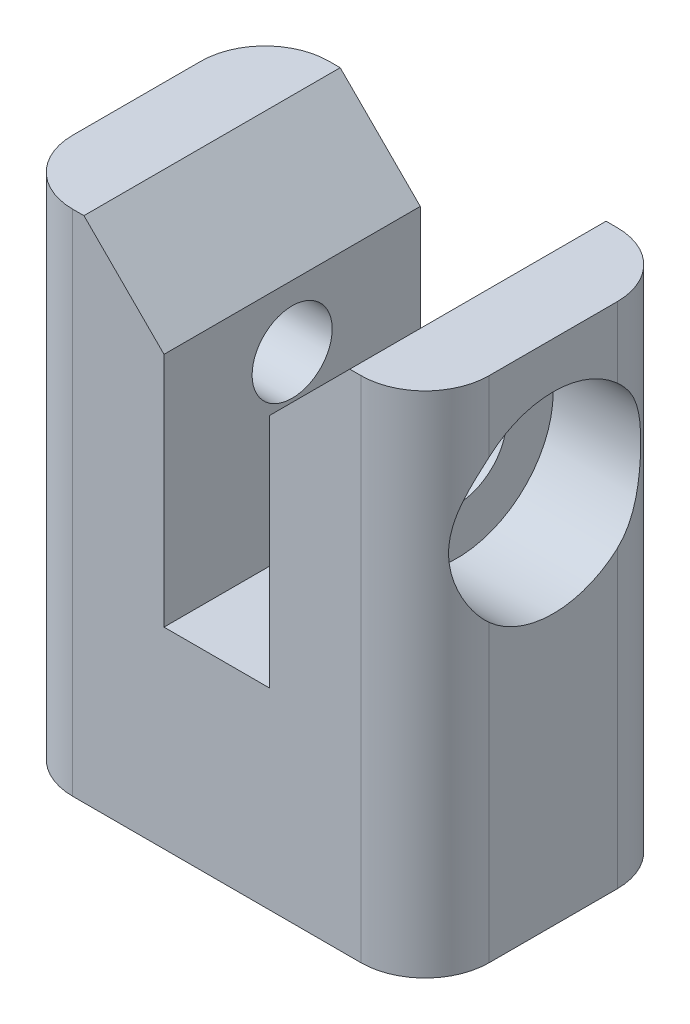
SolidWorks part; units mm, degrees
ref_plane "Front Plane" through (0, 0, 0) normal (0, 0, 1) x (1, 0, 0)
ref_plane "Top Plane" through (0, 0, 0) normal (0, 1, 0) x (1, 0, 0)
ref_plane "Right Plane" through (0, 0, 0) normal (1, 0, 0) x (0, 0, -1)
sketch "Sketch1" plane through (0, 0, 0) normal (0, 0, 1) x (1, 0, 0)
  line L0 (-6.5, 0) -> (6.5, 0)
  line L1 (6.5, 0) -> (6.5, 15.875)
  line L2 (6.5, 15.875) -> (1.65, 15.875)
  line L3 (1.65, 15.875) -> (1.65, 6)
  line L4 (1.65, 6) -> (-1.65, 6)
  line L5 (-1.65, 6) -> (-1.65, 15.875)
  line L6 (-1.65, 15.875) -> (-6.5, 15.875)
  line L7 (-6.5, 15.875) -> (-6.5, 0)
  point P0 (0, 6)
  point P4 (0, 0)
  dimension "D1" = 3.3
  dimension "D2" = 15.875
  dimension "D3" = 6
  dimension "D4" = 13
extrude "Boss-Extrude1" add sketch "Sketch1" along normal mid plane 8
sketch "Sketch2" plane through (6.5, 0, 0) normal (1, 0, 0) x (0, 0, -1)
  line L0 (-4, 6) -> (4, 6) construction
  point P0 (0, 11.4375)
  point P1 (0, 0)
  dimension "D1" = 5.4375
hole_wizard "M3x0.5 Tapped Hole1" positions "Sketch5" profile "Sketch6" tap size "M3x0.5" standard "ANSI Metric" end condition through all
sketch "Sketch5" plane through (6.5, 0, 0) normal (1, 0, 0) x (0, 0, -1)
  point P0 (0, 11.4375)
sketch "Sketch6" plane through (6.5, 11.4375, 0) normal (0, 1, 0) x (0, 0, -1)
  line L0 (0, 0) -> (0, 13)
  line L1 (0, 13) -> (1.25, 13)
  line L2 (1.25, 13) -> (1.25, 0)
  line L5 (1.25, 0) -> (0, 0)
  line L11 (0, -6.35) -> (0, 107.95) construction
  dimension "Thru Tap Drill Dia." = 2.5
  dimension "Thru Tap Drill Depth" = 13
cosmetic thread "Hole Thread1" parameters "D2"=3
hole_wizard "CBORE for M3 SHCS1" positions "Sketch3" profile "Sketch4" counterbore size "M3" standard "ANSI Metric"
sketch "Sketch3" plane through (6.5, 0, 0) normal (1, 0, 0) x (0, 0, -1)
  point P0 (0, 11.4375)
sketch "Sketch4" plane through (6.5, 11.4375, 0) normal (0, 1, 0) x (0, 0, -1)
  line L0 (0, 0) -> (0, 5.7813)
  line L1 (0, 5.7813) -> (1.55, 4.85)
  line L2 (1.55, 4.85) -> (1.55, 3)
  line L3 (1.55, 3) -> (3, 3)
  line L4 (3, 3) -> (3, 0)
  line L5 (3, 0) -> (0, 0)
  line L10 (0, 5.7813) -> (-1.55, 4.85) construction
  line L11 (0, -6.35) -> (0, 107.95) construction
  dimension "Hole Dia." = 3.1
  dimension "Hole Depth" = 4.85
  dimension "C'Bore Dia." = 6
  dimension "C'Bore Depth" = 3
  dimension "Drill Angle" = 118
hole_wizard "M3 Tapped Hole1" positions "Sketch7" profile "Sketch8" tap size "M3" standard "ISO"
sketch "Sketch7" plane through (0, 0, 0) normal (0, -1, 0) x (-1, 0, 0)
  point P0 (0, 0)
sketch "Sketch8" plane through (0, 0, 0) normal (1, 0, 0) x (0, 0, -1)
  line L0 (0, 0) -> (0, 5.7511)
  line L1 (0, 5.7511) -> (1.25, 5)
  line L2 (1.25, 5) -> (1.25, 0)
  line L5 (1.25, 0) -> (0, 0)
  line L10 (0, 5.7511) -> (-1.25, 5) construction
  line L11 (0, -6.35) -> (0, 107.95) construction
  dimension "Tap Drill Dia." = 2.5
  dimension "Tap Drill Depth" = 5
  dimension "Drill Angle" = 118
cosmetic thread "Hole Thread2" parameters "D1"=4, "D2"=3
chamfer "Chamfer1" distance 2.5 angle 45 2 edges at (-1.65, 15.875, 0) (1.65, 15.875, 0)
fillet "Fillet1" radius 2 4 edges at (-6.5, 7.9375, 4) (6.5, 7.9375, 4) (-6.5, 7.9375, -4) (6.5, 7.9375, -4)
